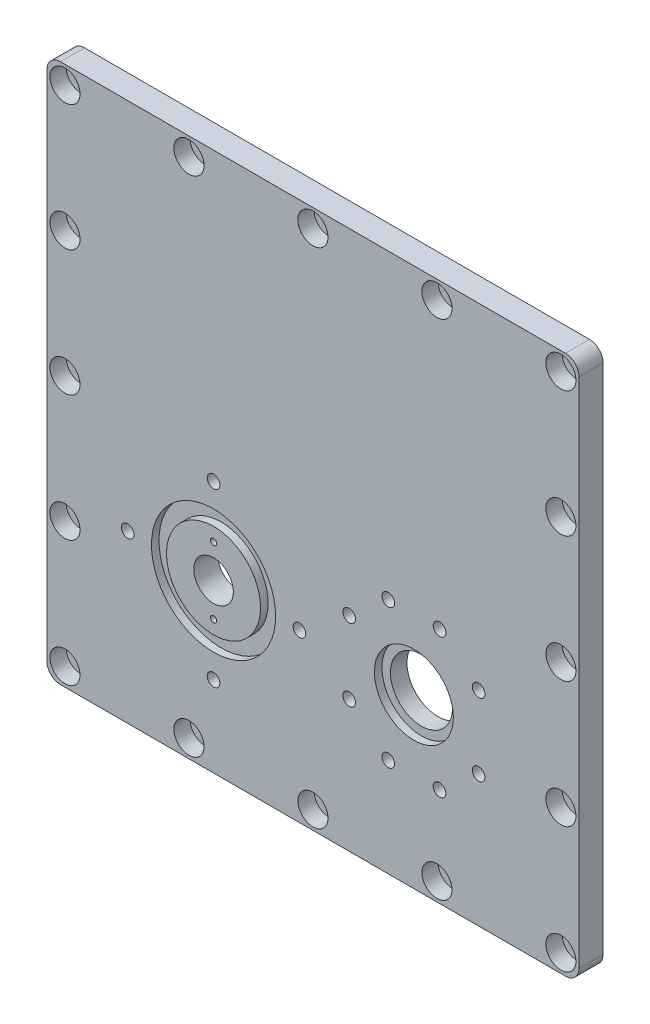
SolidWorks part; units mm, degrees
ref_plane "Front Plane" through (0, 0, 0) normal (0, 0, 1) x (1, 0, 0)
ref_plane "Top Plane" through (0, 0, 0) normal (0, 1, 0) x (1, 0, 0)
ref_plane "Right Plane" through (0, 0, 0) normal (1, 0, 0) x (0, 0, -1)
sketch "Sketch1" plane through (0, 0, 0) normal (0, 0, 1) x (1, 0, 0)
  line L24 (-83.7906, -89.5) -> (83.7906, -89.5)
  line L25 (-88.2906, 85) -> (-88.2906, -85)
  line L26 (83.7906, 89.5) -> (-83.7906, 89.5)
  line L27 (88.2906, -85) -> (88.2906, 85)
  line L28 (-83.7906, -89.5) -> (83.7906, -89.5)
  line L29 (-88.2906, 85) -> (-88.2906, -85)
  line L30 (83.7906, 89.5) -> (-83.7906, 89.5)
  line L31 (88.2906, -85) -> (88.2906, 85)
  arc A21 (83.7906, -89.5) -> (88.2906, -85) centre (83.7906, -85) ccw
  arc A22 (-88.2906, -85) -> (-83.7906, -89.5) centre (-83.7906, -85) ccw
  arc A23 (-83.7906, 89.5) -> (-88.2906, 85) centre (-83.7906, 85) ccw
  arc A24 (88.2906, 85) -> (83.7906, 89.5) centre (83.7906, 85) ccw
  arc A25 (83.7906, -89.5) -> (88.2906, -85) centre (83.7906, -85) ccw
  arc A26 (-88.2906, -85) -> (-83.7906, -89.5) centre (-83.7906, -85) ccw
  arc A27 (-83.7906, 89.5) -> (-88.2906, 85) centre (-83.7906, 85) ccw
  arc A28 (88.2906, 85) -> (83.7906, 89.5) centre (83.7906, 85) ccw
  dimension "D1" = 0.5
extrude "Boss-Extrude1" add sketch "Sketch1" along normal up to surface (8 mm away)
sketch "Sketch2" plane through (0, 0, 8) normal (0, 0, 1) x (1, 0, 0)
  line L0 (-74.25, -98) -> (-69.25, -98) construction
  line L1 (-74.25, -98) -> (-69.25, -98) construction
  line L2 (2.1, 83.5) -> (0, 83.5)
  line L3 (0, 83.5) -> (-2.1, 83.5)
  line L4 (2.1, 83.5) -> (0, 83.5) construction
  line L5 (0, 83.5) -> (-2.1, 83.5) construction
  line L7 (-74.25, -98.5) -> (-69.25, -98.5)
  line L8 (2.5515, 84) -> (0, 84)
  line L9 (0, 84) -> (-2.5515, 84)
  arc A0 (43.2453, 83.5) -> (39.0453, 83.5) centre (41.1453, 83.5) ccw construction
  arc A1 (39.0453, 83.5) -> (43.2453, 83.5) centre (41.1453, 83.5) ccw construction
  arc A2 (43.2453, 83.5) -> (39.0453, 83.5) centre (41.1453, 83.5) ccw construction
  arc A3 (39.0453, 83.5) -> (43.2453, 83.5) centre (41.1453, 83.5) ccw construction
  arc A4 (2.1, 83.5) -> (-2.1, 83.5) centre (0, 83.5) ccw construction
  arc A5 (-2.1, 83.5) -> (2.1, 83.5) centre (0, 83.5) ccw
  arc A6 (-2.1, 83.5) -> (2.1, 83.5) centre (0, 83.5) ccw construction
  arc A7 (2.1, 83.5) -> (-2.1, 83.5) centre (0, 83.5) ccw construction
  arc A8 (-84.3906, -41.75) -> (-80.1906, -41.75) centre (-82.2906, -41.75) ccw construction
  arc A9 (-80.1906, -41.75) -> (-84.3906, -41.75) centre (-82.2906, -41.75) ccw construction
  arc A10 (-84.3906, 0) -> (-80.1906, 0) centre (-82.2906, 0) ccw construction
  arc A11 (-80.1906, 0) -> (-84.3906, 0) centre (-82.2906, 0) ccw construction
  arc A12 (-43.2453, 83.5) -> (-39.0453, 83.5) centre (-41.1453, 83.5) ccw construction
  arc A13 (-84.3906, 83.5) -> (-80.1906, 83.5) centre (-82.2906, 83.5) ccw construction
  arc A14 (-84.3906, 41.75) -> (-80.1906, 41.75) centre (-82.2906, 41.75) ccw construction
  arc A15 (-80.1906, 41.75) -> (-84.3906, 41.75) centre (-82.2906, 41.75) ccw construction
  arc A16 (-80.1906, 83.5) -> (-84.3906, 83.5) centre (-82.2906, 83.5) ccw construction
  arc A17 (-39.0453, 83.5) -> (-43.2453, 83.5) centre (-41.1453, 83.5) ccw construction
  arc A18 (-84.3906, -41.75) -> (-80.1906, -41.75) centre (-82.2906, -41.75) ccw construction
  arc A19 (-80.1906, -41.75) -> (-84.3906, -41.75) centre (-82.2906, -41.75) ccw construction
  arc A20 (-84.3906, 0) -> (-80.1906, 0) centre (-82.2906, 0) ccw construction
  arc A21 (-80.1906, 0) -> (-84.3906, 0) centre (-82.2906, 0) ccw construction
  arc A22 (-43.2453, 83.5) -> (-39.0453, 83.5) centre (-41.1453, 83.5) ccw construction
  arc A23 (-84.3906, 83.5) -> (-80.1906, 83.5) centre (-82.2906, 83.5) ccw construction
  arc A24 (-84.3906, 41.75) -> (-80.1906, 41.75) centre (-82.2906, 41.75) ccw construction
  arc A25 (-80.1906, 41.75) -> (-84.3906, 41.75) centre (-82.2906, 41.75) ccw construction
  arc A26 (-80.1906, 83.5) -> (-84.3906, 83.5) centre (-82.2906, 83.5) ccw construction
  arc A27 (-39.0453, 83.5) -> (-43.2453, 83.5) centre (-41.1453, 83.5) ccw construction
  arc A28 (80.1906, -41.75) -> (84.3906, -41.75) centre (82.2906, -41.75) ccw construction
  arc A29 (84.3906, -41.75) -> (80.1906, -41.75) centre (82.2906, -41.75) ccw construction
  arc A30 (80.1906, -83.5) -> (84.3906, -83.5) centre (82.2906, -83.5) ccw construction
  arc A31 (84.3906, -83.5) -> (80.1906, -83.5) centre (82.2906, -83.5) ccw construction
  arc A32 (39.0453, -83.5) -> (43.2453, -83.5) centre (41.1453, -83.5) ccw construction
  arc A33 (43.2453, -83.5) -> (39.0453, -83.5) centre (41.1453, -83.5) ccw construction
  arc A34 (-2.1, -83.5) -> (2.1, -83.5) centre (0, -83.5) ccw construction
  arc A35 (2.1, -83.5) -> (-2.1, -83.5) centre (0, -83.5) ccw construction
  arc A36 (-43.2453, -83.5) -> (-39.0453, -83.5) centre (-41.1453, -83.5) ccw construction
  arc A37 (-39.0453, -83.5) -> (-43.2453, -83.5) centre (-41.1453, -83.5) ccw construction
  arc A38 (-80.1906, -83.5) -> (-84.3906, -83.5) centre (-82.2906, -83.5) ccw construction
  arc A39 (-84.3906, -83.5) -> (-80.1906, -83.5) centre (-82.2906, -83.5) ccw construction
  arc A40 (80.1906, -41.75) -> (84.3906, -41.75) centre (82.2906, -41.75) ccw construction
  arc A41 (84.3906, -41.75) -> (80.1906, -41.75) centre (82.2906, -41.75) ccw construction
  arc A42 (80.1906, -83.5) -> (84.3906, -83.5) centre (82.2906, -83.5) ccw construction
  arc A43 (84.3906, -83.5) -> (80.1906, -83.5) centre (82.2906, -83.5) ccw construction
  arc A44 (39.0453, -83.5) -> (43.2453, -83.5) centre (41.1453, -83.5) ccw construction
  arc A45 (43.2453, -83.5) -> (39.0453, -83.5) centre (41.1453, -83.5) ccw construction
  arc A46 (-2.1, -83.5) -> (2.1, -83.5) centre (0, -83.5) ccw construction
  arc A47 (2.1, -83.5) -> (-2.1, -83.5) centre (0, -83.5) ccw construction
  arc A48 (-43.2453, -83.5) -> (-39.0453, -83.5) centre (-41.1453, -83.5) ccw construction
  arc A49 (-39.0453, -83.5) -> (-43.2453, -83.5) centre (-41.1453, -83.5) ccw construction
  arc A50 (-80.1906, -83.5) -> (-84.3906, -83.5) centre (-82.2906, -83.5) ccw construction
  arc A51 (-84.3906, -83.5) -> (-80.1906, -83.5) centre (-82.2906, -83.5) ccw construction
  arc A52 (80.1906, 83.5) -> (84.3906, 83.5) centre (82.2906, 83.5) ccw construction
  arc A53 (84.3906, 83.5) -> (80.1906, 83.5) centre (82.2906, 83.5) ccw construction
  arc A54 (80.1906, 41.75) -> (84.3906, 41.75) centre (82.2906, 41.75) ccw construction
  arc A55 (84.3906, 41.75) -> (80.1906, 41.75) centre (82.2906, 41.75) ccw construction
  arc A56 (80.1906, 0) -> (84.3906, 0) centre (82.2906, 0) ccw construction
  arc A57 (84.3906, 0) -> (80.1906, 0) centre (82.2906, 0) ccw construction
  arc A58 (80.1906, 83.5) -> (84.3906, 83.5) centre (82.2906, 83.5) ccw construction
  arc A59 (84.3906, 83.5) -> (80.1906, 83.5) centre (82.2906, 83.5) ccw construction
  arc A60 (80.1906, 41.75) -> (84.3906, 41.75) centre (82.2906, 41.75) ccw construction
  arc A61 (84.3906, 41.75) -> (80.1906, 41.75) centre (82.2906, 41.75) ccw construction
  arc A62 (80.1906, 0) -> (84.3906, 0) centre (82.2906, 0) ccw construction
  arc A63 (84.3906, 0) -> (80.1906, 0) centre (82.2906, 0) ccw construction
  arc A64 (-2.5515, 84) -> (2.5515, 84) centre (0, 83.5) ccw
  arc A65 (43.7453, 83.5) -> (38.5453, 83.5) centre (41.1453, 83.5) ccw
  arc A66 (38.5453, 83.5) -> (43.7453, 83.5) centre (41.1453, 83.5) ccw
  arc A67 (2.6, 83.5) -> (-2.6, 83.5) centre (0, 83.5) ccw
  arc A68 (-84.8906, -41.75) -> (-79.6906, -41.75) centre (-82.2906, -41.75) ccw
  arc A69 (-79.6906, -41.75) -> (-84.8906, -41.75) centre (-82.2906, -41.75) ccw
  arc A70 (-84.8906, 0) -> (-79.6906, 0) centre (-82.2906, 0) ccw
  arc A71 (-79.6906, 0) -> (-84.8906, 0) centre (-82.2906, 0) ccw
  arc A72 (-43.7453, 83.5) -> (-38.5453, 83.5) centre (-41.1453, 83.5) ccw
  arc A73 (-38.5453, 83.5) -> (-43.7453, 83.5) centre (-41.1453, 83.5) ccw
  arc A74 (-84.8906, 83.5) -> (-79.6906, 83.5) centre (-82.2906, 83.5) ccw
  arc A75 (-79.6906, 83.5) -> (-84.8906, 83.5) centre (-82.2906, 83.5) ccw
  arc A76 (-84.8906, 41.75) -> (-79.6906, 41.75) centre (-82.2906, 41.75) ccw
  arc A77 (-79.6906, 41.75) -> (-84.8906, 41.75) centre (-82.2906, 41.75) ccw
  arc A78 (79.6906, -41.75) -> (84.8906, -41.75) centre (82.2906, -41.75) ccw
  arc A79 (84.8906, -41.75) -> (79.6906, -41.75) centre (82.2906, -41.75) ccw
  arc A80 (79.6906, -83.5) -> (84.8906, -83.5) centre (82.2906, -83.5) ccw
  arc A81 (84.8906, -83.5) -> (79.6906, -83.5) centre (82.2906, -83.5) ccw
  arc A82 (38.5453, -83.5) -> (43.7453, -83.5) centre (41.1453, -83.5) ccw
  arc A83 (43.7453, -83.5) -> (38.5453, -83.5) centre (41.1453, -83.5) ccw
  arc A84 (-2.6, -83.5) -> (2.6, -83.5) centre (0, -83.5) ccw
  arc A85 (2.6, -83.5) -> (-2.6, -83.5) centre (0, -83.5) ccw
  arc A86 (-43.7453, -83.5) -> (-38.5453, -83.5) centre (-41.1453, -83.5) ccw
  arc A87 (-38.5453, -83.5) -> (-43.7453, -83.5) centre (-41.1453, -83.5) ccw
  arc A88 (-79.6906, -83.5) -> (-84.8906, -83.5) centre (-82.2906, -83.5) ccw
  arc A89 (-84.8906, -83.5) -> (-79.6906, -83.5) centre (-82.2906, -83.5) ccw
  arc A90 (79.6906, 83.5) -> (84.8906, 83.5) centre (82.2906, 83.5) ccw
  arc A91 (84.8906, 83.5) -> (79.6906, 83.5) centre (82.2906, 83.5) ccw
  arc A92 (79.6906, 41.75) -> (84.8906, 41.75) centre (82.2906, 41.75) ccw
  arc A93 (84.8906, 41.75) -> (79.6906, 41.75) centre (82.2906, 41.75) ccw
  arc A94 (79.6906, 0) -> (84.8906, 0) centre (82.2906, 0) ccw
  arc A95 (84.8906, 0) -> (79.6906, 0) centre (82.2906, 0) ccw
  dimension "D1" = 0
  dimension "D2" = 0.5
extrude "Cut-Extrude1" cut sketch "Sketch2" against normal blind 90 contours A65 A66 | L8 A67 L9 | L9 A64 L8 | A72 A73 | A74 A75 | A76 A77 | A70 A71 | A88 A89 | A68 A69 | A86 A87 | A84 A85 | A82 A83 | A80 A81 | A78 A79 | A94 A95 | A92 A93 | A90 A91 region at (2.5276, 83.7453, 8) region at (0, 84.8782, 8) region at (41.1453, 83.5, 8) region at (-82.2906, -41.75, 8) region at (-82.2906, 0, 8) region at (-41.1453, 83.5, 8) region at (-82.2906, 83.5, 8) region at (-82.2906, 41.75, 8) region at (82.2906, -41.75, 8) region at (82.2906, -83.5, 8) region at (41.1453, -83.5, 8) region at (0, -83.5, 8) region at (-41.1453, -83.5, 8) region at (-82.2906, -83.5, 8) region at (82.2906, 83.5, 8) region at (82.2906, 41.75, 8) region at (82.2906, 0, 8) body kept at (-83.7906, -89.5, 0)
sketch "Sketch3" plane through (0, 0, 8) normal (0, 0, 1) x (1, 0, 0)
  circle A0 centre (41.1453, 83.5) radius 5
  circle A1 centre (41.1453, 83.5) radius 2.6
  circle A2 centre (41.1453, 83.5) radius 2.6 construction
  circle A3 centre (82.2906, 83.5) radius 2.6
  circle A4 centre (82.2906, 83.5) radius 2.6 construction
  circle A5 centre (82.2906, 41.75) radius 2.6
  circle A6 centre (82.2906, 41.75) radius 2.6 construction
  circle A7 centre (82.2906, 0) radius 2.6
  circle A8 centre (82.2906, 0) radius 2.6 construction
  circle A9 centre (82.2906, -41.75) radius 2.6
  circle A10 centre (82.2906, -41.75) radius 2.6 construction
  circle A11 centre (82.2906, -83.5) radius 2.6
  circle A12 centre (82.2906, -83.5) radius 2.6 construction
  circle A13 centre (41.1453, -83.5) radius 2.6
  circle A14 centre (41.1453, -83.5) radius 2.6 construction
  circle A15 centre (0, -83.5) radius 2.6
  circle A16 centre (0, -83.5) radius 2.6 construction
  circle A17 centre (-82.2906, 0) radius 2.6
  circle A18 centre (-82.2906, 0) radius 2.6 construction
  circle A19 centre (-82.2906, -83.5) radius 2.6
  circle A20 centre (-82.2906, -83.5) radius 2.6 construction
  circle A21 centre (-82.2906, -41.75) radius 2.6
  circle A22 centre (-82.2906, -41.75) radius 2.6 construction
  circle A23 centre (-41.1453, -83.5) radius 2.6
  circle A24 centre (-41.1453, -83.5) radius 2.6 construction
  circle A25 centre (-82.2906, 41.75) radius 2.6
  circle A26 centre (-82.2906, 41.75) radius 2.6 construction
  circle A27 centre (-82.2906, 83.5) radius 2.6
  circle A28 centre (-82.2906, 83.5) radius 2.6 construction
  circle A29 centre (-41.1453, 83.5) radius 2.6
  circle A30 centre (-41.1453, 83.5) radius 2.6 construction
  circle A31 centre (0, 83.5) radius 2.6
  circle A32 centre (0, 83.5) radius 2.6 construction
  circle A33 centre (82.2906, 83.5) radius 5
  circle A34 centre (82.2906, 41.75) radius 5
  circle A35 centre (82.2906, 0) radius 5
  circle A36 centre (82.2906, -41.75) radius 5
  circle A37 centre (82.2906, -83.5) radius 5
  circle A38 centre (41.1453, -83.5) radius 5
  circle A39 centre (0, -83.5) radius 5
  circle A40 centre (-82.2906, 0) radius 5
  circle A41 centre (-82.2906, -83.5) radius 5
  circle A42 centre (-82.2906, -41.75) radius 5
  circle A43 centre (-41.1453, -83.5) radius 5
  circle A44 centre (-82.2906, 41.75) radius 5
  circle A45 centre (-82.2906, 83.5) radius 5
  circle A46 centre (-41.1453, 83.5) radius 5
  circle A47 centre (0, 83.5) radius 5
  dimension "D1" = 0
  dimension "D2" = 0
  dimension "D3" = 0
  dimension "D4" = 0
  dimension "D5" = 0
  dimension "D6" = 0
  dimension "D7" = 0
  dimension "D8" = 0
  dimension "D9" = 0
  dimension "D10" = 0
  dimension "D11" = 0
  dimension "D12" = 0
  dimension "D13" = 0
  dimension "D14" = 0
  dimension "D15" = 0
  dimension "D16" = 0
  dimension "D17" = 2.4
extrude "Cut-Extrude2" cut sketch "Sketch3" against normal blind 5.4
sketch "Sketch5" plane through (0, 0, 8) normal (0, 0, 1) x (1, 0, 0)
  circle A5 centre (33.4966, -33.7548) radius 10.3
extrude "Cut-Extrude3" cut sketch "Sketch5" against normal blind 20
sketch "Sketch6" plane through (0, 0, 8) normal (0, 0, 1) x (1, 0, 0)
  circle A4 centre (33.4966, -33.7548) radius 9
  circle A5 centre (33.4966, -33.7548) radius 7.5
  dimension "D1" = 18
  dimension "D2" = 15
sketch "Sketch7" plane through (0, 0, 8) normal (0, 0, 1) x (1, 0, 0)
  circle A4 centre (-32.9906, -34.2) radius 15.6
  circle A5 centre (-32.9906, -34.2) radius 20.6
extrude "Cut-Extrude5" cut sketch "Sketch7" against normal blind 2.5
sketch "Sketch9" plane through (0, 0, 8) normal (0, 0, 1) x (1, 0, 0)
  circle A0 centre (-32.9906, -34.2) radius 6.575 construction
  circle A1 centre (-32.9906, -34.2) radius 6.575
  circle A2 centre (-32.9906, -5.7) radius 2.1
  circle A3 centre (-32.9906, -23.0748) radius 1.025
  circle A4 centre (-32.9906, -23.0748) radius 1.025
  circle A5 centre (-32.9906, -45.3252) radius 1.025
  circle A6 centre (-32.9906, -45.3252) radius 1.025
  circle A7 centre (-32.9906, -34.2) radius 8.875
  circle A8 centre (-32.9906, -34.2) radius 8.875
  circle A9 centre (-32.9906, -45.3252) radius 1.025
  circle A11 centre (-32.9906, -45.3252) radius 1.025
  circle A13 centre (-32.9906, -23.0748) radius 1.025
  circle A15 centre (-32.9906, -23.0748) radius 1.025
  circle A17 centre (-32.9906, -34.2) radius 8.875
  circle A18 centre (-32.9906, -34.2) radius 8.875
  circle A19 centre (-4.4906, -34.2) radius 2.65
  circle A20 centre (-4.4906, -34.2) radius 2.65 construction
  circle A21 centre (-32.9906, -62.7) radius 2.65
  circle A22 centre (-32.9906, -62.7) radius 2.65 construction
  circle A23 centre (-61.4906, -34.2) radius 2.65
  circle A24 centre (-61.4906, -34.2) radius 2.65 construction
  circle A25 centre (-32.9906, -5.7) radius 2.65
  circle A26 centre (-32.9906, -5.7) radius 2.65 construction
  circle A27 centre (-4.4906, -34.2) radius 2.1
  circle A28 centre (-32.9906, -62.7) radius 2.1
  circle A29 centre (-61.4906, -34.2) radius 2.1
  dimension "D13" = 4.2
  dimension "D1" = 0
  dimension "D2" = 0
  dimension "D3" = 0
  dimension "D4" = 0
  dimension "D5" = 0
  dimension "D6" = 0
  dimension "D7" = 0
  dimension "D8" = 0
  dimension "D9" = 0
  dimension "D10" = 0
extrude "Cut-Extrude6" cut sketch "Sketch9" against normal up to next contours A11 | A20 | A15 | A29 | A28 | A2 | A27 | A1 region at (-32.9906, -34.2, 8) region at (-32.9906, -5.7, 8) region at (-32.9906, -23.0748, 8) region at (-32.9906, -45.3252, 8) region at (-4.4906, -34.2, 8) region at (-32.9906, -62.7, 8) region at (-61.4906, -34.2, 8)
sketch "Sketch10" plane through (0, 0, 8) normal (0, 0, 1) x (1, 0, 0)
  circle A3 centre (12.022, -45.7548) radius 2.65 construction
  circle A11 centre (24.9966, -56.8396) radius 2.65 construction
  circle A15 centre (41.9966, -56.8396) radius 2.65 construction
  circle A19 centre (54.9713, -45.7548) radius 2.65 construction
  circle A30 centre (12.022, -21.7548) radius 2.65 construction
  circle A32 centre (24.9966, -10.6699) radius 2.65 construction
  circle A34 centre (41.9966, -10.6699) radius 2.65 construction
  circle A35 centre (54.9713, -21.7548) radius 2.1
  circle A36 centre (54.9713, -21.7548) radius 2.65 construction
  circle A37 centre (41.9966, -10.6699) radius 2.1
  circle A38 centre (24.9966, -10.6699) radius 2.1
  circle A39 centre (12.022, -21.7548) radius 2.1
  circle A40 centre (12.022, -45.7548) radius 2.1
  circle A41 centre (24.9966, -56.8396) radius 2.1
  circle A42 centre (41.9966, -56.8396) radius 2.1
  circle A43 centre (54.9713, -45.7548) radius 2.1
  dimension "D2" = 4.2
extrude "Cut-Extrude10" cut sketch "Sketch10" against normal blind 10 contours A38 | A40 | A41 | A42 | A35 | A34 | A37 | A39 | A43 region at (24.9966, -10.6699, 8) region at (12.022, -45.7548, 8) region at (24.9966, -56.8396, 8) region at (41.9966, -56.8396, 8)
sketch "Sketch11" plane through (0, 0, 8) normal (0, 0, 1) x (1, 0, 0)
  arc A1 (33.4966, -20.6548) -> (33.4966, -46.8548) centre (33.4966, -33.7548) ccw
  arc A3 (33.4966, -46.8548) -> (33.4966, -20.6548) centre (33.4966, -33.7548) ccw
extrude "Cut-Extrude11" cut sketch "Sketch11" against normal blind 2.5
sketch "Sketch12" plane through (0, 0, 0) normal (0, 0, -1) x (-1, 0, 0)
  circle A0 centre (32.9906, -23.0748) radius 1.025 construction
  circle A1 centre (32.9906, -23.0748) radius 1.025
  circle A2 centre (32.9906, -45.3252) radius 1.025 construction
  circle A3 centre (32.9906, -45.3252) radius 1.025
extrude "Boss-Extrude2" add sketch "Sketch12" against normal blind 1
fillet "Fillet1" radius 0.5 2 edges at (-34.0156, -23.0748, 1) (-34.0156, -45.3252, 1)
